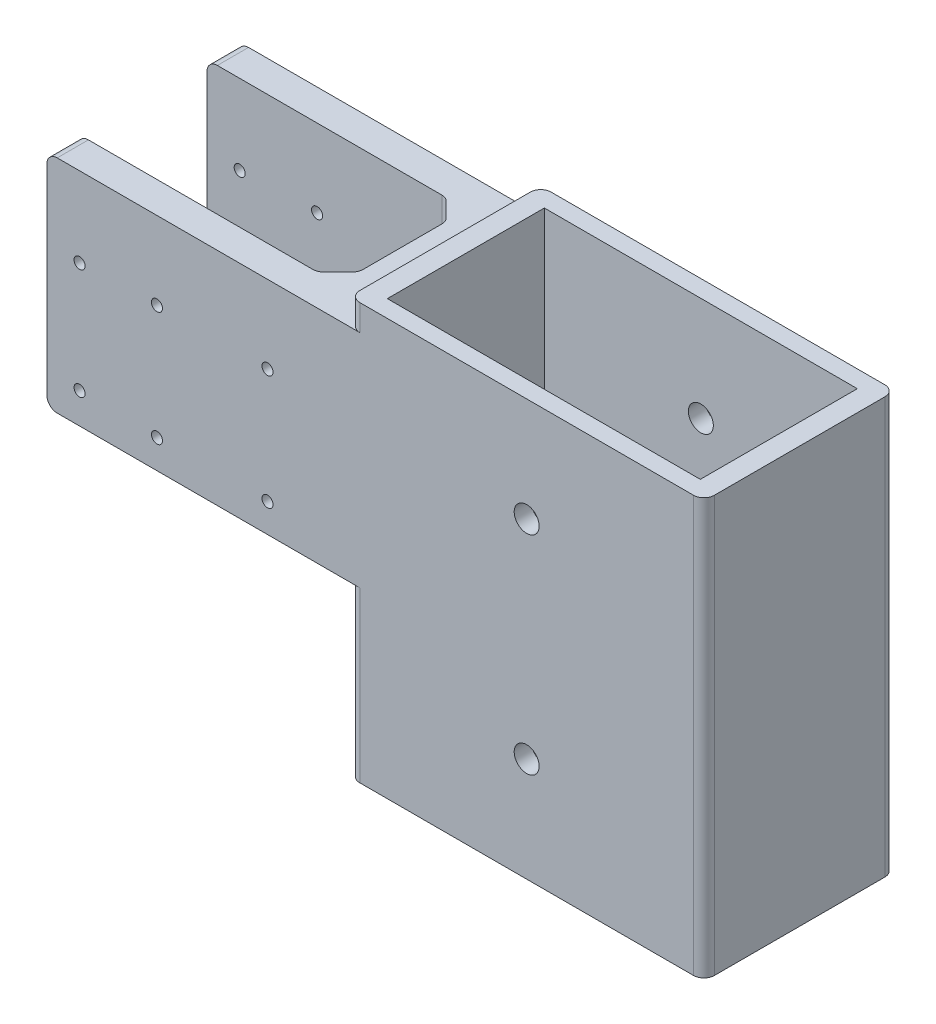
SolidWorks part; units mm, degrees
ref_plane "Front Plane" through (0, 0, 0) normal (0, 0, 1) x (1, 0, 0)
ref_plane "Top Plane" through (0, 0, 0) normal (0, 1, 0) x (1, 0, 0)
ref_plane "Right Plane" through (0, 0, 0) normal (1, 0, 0) x (0, 0, -1)
sketch "Sketch1" plane through (0, 0, 0) normal (0, 0, 1) x (1, 0, 0)
  line L0 (-45.9066, 14) -> (0, 14) construction
  line L1 (-53.9066, 47) -> (-53.9066, -7)
  line L3 (106.614, -48.25) -> (106.614, 53.35)
  line L7 (-53.9066, -7) -> (20, -7)
  line L8 (20, -7) -> (20, -48.25)
  line L9 (20, -48.25) -> (106.614, -48.25)
  line L10 (-53.9066, 47) -> (20, 47)
  line L11 (20, 47) -> (20, 53.35)
  line L12 (20, 53.35) -> (106.614, 53.35)
  circle A0 centre (0, 0) radius 1.35
  circle A1 centre (-27, 0) radius 1.35
  circle A2 centre (-45.9066, 0.5) radius 1.35
  circle A3 centre (-45.9066, 27.5) radius 1.35
  circle A4 centre (-27, 28) radius 1.35
  circle A5 centre (0, 28) radius 1.35
  point P15 (0, 0)
  point P20 (0, 0)
  point P26 (49.1989, 44.9395)
  dimension "D1" = 2.7
  dimension "D2" = 28
  dimension "D3" = 27
  dimension "D4" = 27
  dimension "D5" = 18.9066
  dimension "D6" = 8
  dimension "D7" = 19.5
  dimension "D8" = 7.5
  dimension "D9" = 20
  dimension "D10" = 86.614
  dimension "D11" = 101.6
  dimension "D12" = 6.35
extrude "Boss-Extrude1" add sketch "Sketch1" along normal blind 46.736
sketch "Sketch2" plane through (0, 53.35, 0) normal (0, 1, 0) x (1, 0, 0)
  line L0 (-53.9066, -7.62) -> (4.5134, -7.62)
  line L1 (25.08, -42.545) -> (101.534, -42.545)
  line L2 (25.08, -42.545) -> (25.08, -4.191)
  line L3 (25.08, -4.191) -> (101.534, -4.191)
  line L4 (101.534, -42.545) -> (101.534, -4.191)
  line L5 (25.08, -42.545) -> (101.534, -4.191) construction
  line L6 (25.08, -4.191) -> (101.534, -42.545) construction
  line L7 (-53.9066, -46.736) -> (-53.9066, 0) construction
  line L10 (4.5134, -39.116) -> (-53.9066, -39.116)
  line L11 (-53.9066, -39.116) -> (-53.9066, -7.62)
  line L12 (4.5134, -7.62) -> (9.5934, -12.7)
  line L13 (9.5934, -12.7) -> (9.5934, -34.036)
  line L14 (9.5934, -34.036) -> (4.5134, -39.116)
  line L15 (20, -46.736) -> (20, 0) construction
  line L16 (106.614, -23.368) -> (101.534, -23.368) construction
  line L17 (106.614, -46.736) -> (106.614, 0) construction
  line L18 (20, 0) -> (-53.9066, 0) construction
  point P0 (63.307, -23.368)
  point P17 (9.5934, -23.368)
  point P23 (8.3003, -7.62)
  point P24 (9.3342, -11.9123)
  point P25 (9.5934, -12.1402)
  dimension "D1" = 38.354
  dimension "D2" = 76.454
  dimension "D3" = 5.08
  dimension "D4" = 7.62
  dimension "D5" = 58.42
  dimension "D6" = 5.08
  dimension "D7" = 225
extrude "Cut-Extrude1" cut sketch "Sketch2" against normal blind 137.16
fillet "Fillet1" radius 2.54 14 edges at (106.614, 2.55, 0) (106.614, 2.55, 46.736) (4.5134, 20, 39.116) (9.5934, 20, 34.036) (9.5934, 20, 12.7) (4.5134, 20, 7.62) (20, 50.175, 0) (20, 50.175, 46.736) (20, -27.625, 0) (20, -27.625, 46.736) (-53.9066, -7, 42.926) (-53.9066, -7, 3.81) (-53.9066, 47, 3.81) (-53.9066, 47, 42.926)
sketch "Sketch3" plane through (0, 0, 46.736) normal (0, 0, 1) x (1, 0, 0)
  line L0 (63.307, 53.35) -> (63.307, 27.95) construction
  line L1 (104.074, 53.35) -> (22.54, 53.35) construction
  line L2 (22.54, -48.25) -> (104.074, -48.25) construction
  circle A0 centre (63.307, 27.95) radius 3.05
  circle A1 centre (63.307, -22.85) radius 3.05
  point P5 (63.307, 35.4103)
  dimension "D1" = 6.1
  dimension "D2" = 25.4
  dimension "D3" = 25.4
extrude "Cut-Extrude2" cut sketch "Sketch3" against normal blind 66.294
